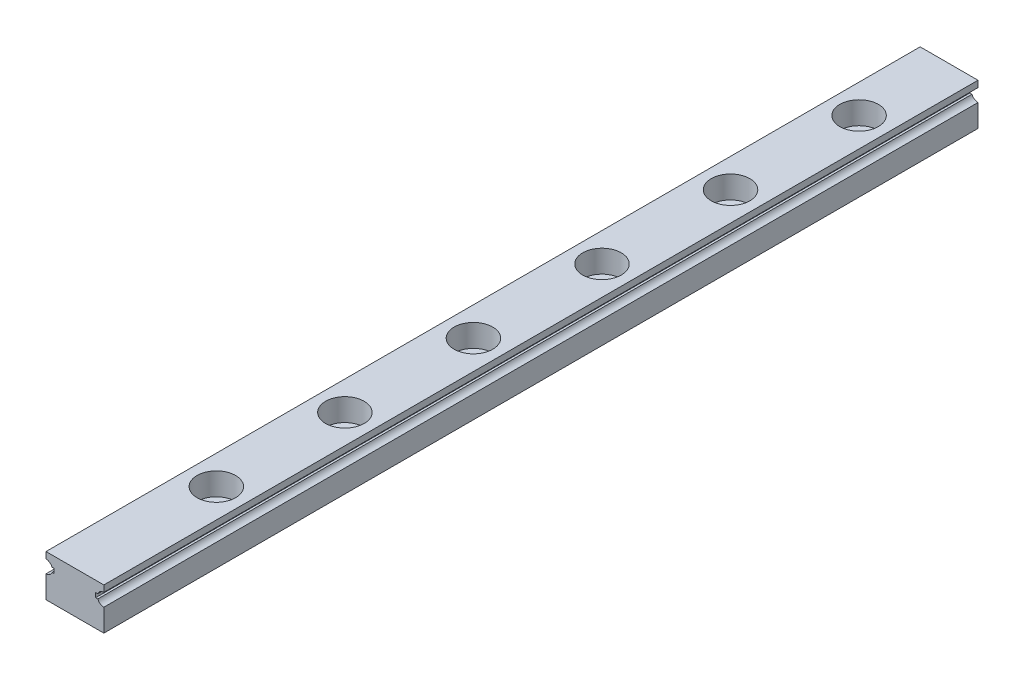
SolidWorks part; units mm, degrees
material "Сталь 40 ГОСТ 535-88"
ref_plane "Спереди" through (0, 0, 0) normal (0, 0, 1) x (1, 0, 0)
ref_plane "Сверху" through (0, 0, 0) normal (0, 1, 0) x (1, 0, 0)
ref_plane "Справа" through (0, 0, 0) normal (1, 0, 0) x (0, 0, -1)
sketch "Sketch1" plane through (0, 0, 0) normal (0, 0, 1) x (1, 0, 0)
  line L0 (0, 0) -> (0, 5.7299) construction
  line L1 (-4.5, -3.25) -> (4.5, -3.25)
  line L2 (-4.5, -3.25) -> (-4.5, 0.25)
  line L3 (-4.5, 3.25) -> (4.5, 3.25)
  line L4 (4.5, -3.25) -> (4.5, 0.25)
  line L5 (-4.5, -3.25) -> (4.5, 3.25) construction
  line L6 (-4.5, 3.25) -> (4.5, -3.25) construction
  line L7 (-4.5, 2.25) -> (-4.5, 3.25)
  line L8 (-3.564, 0.898) -> (-3.2351, 0.898)
  line L9 (3.564, 0.898) -> (3.2351, 0.898)
  line L10 (-3.564, 1.602) -> (-3.2351, 1.602)
  line L11 (-3.2351, 0.898) -> (-3.2351, 1.602)
  line L12 (3.2351, 0.898) -> (3.2351, 1.602)
  line L13 (3.564, 1.602) -> (3.2351, 1.602)
  line L14 (4.5, 2.25) -> (4.5, 3.25)
  arc A0 (-3.564, 1.602) -> (-4.5, 2.25) centre (-4.5, 1.25) ccw
  arc A1 (-4.5, 0.25) -> (-3.564, 0.898) centre (-4.5, 1.25) ccw
  arc A2 (4.5, 0.25) -> (3.564, 0.898) centre (4.5, 1.25) cw
  arc A3 (3.564, 1.602) -> (4.5, 2.25) centre (4.5, 1.25) cw
  point P0 (0, 0)
  dimension "D3" = 1
  dimension "D1" = 9
  dimension "D2" = 6.5
  dimension "D4" = 2
extrude "Extrude1" add sketch "Sketch1" along normal blind 136
sketch "Sketch2" plane through (0, 3.25, 0) normal (0, 1, 0) x (1, 0, 0)
  line L0 (4.5, 0) -> (-4.5, 0) construction
  circle A0 centre (0, -14) radius 1.75
  circle A1 centre (0, -14) radius 3
  dimension "D1" = 3.5
  dimension "D2" = 6
  dimension "D3" = 14
extrude "Extrude2" cut sketch "Sketch2" against normal blind 3.5 contours A1
extrude "Extrude3" cut sketch "Sketch" against normal through all contours A0
sketch "Sketch" plane through (0, 3.25, 0) normal (0, 1, 0) x (1, 0, 0) same geometry as "Sketch2"
pattern_linear "LPattern1" count 6 spacing 20 along (0, 0, 1) of "Extrude2", "Extrude3"
